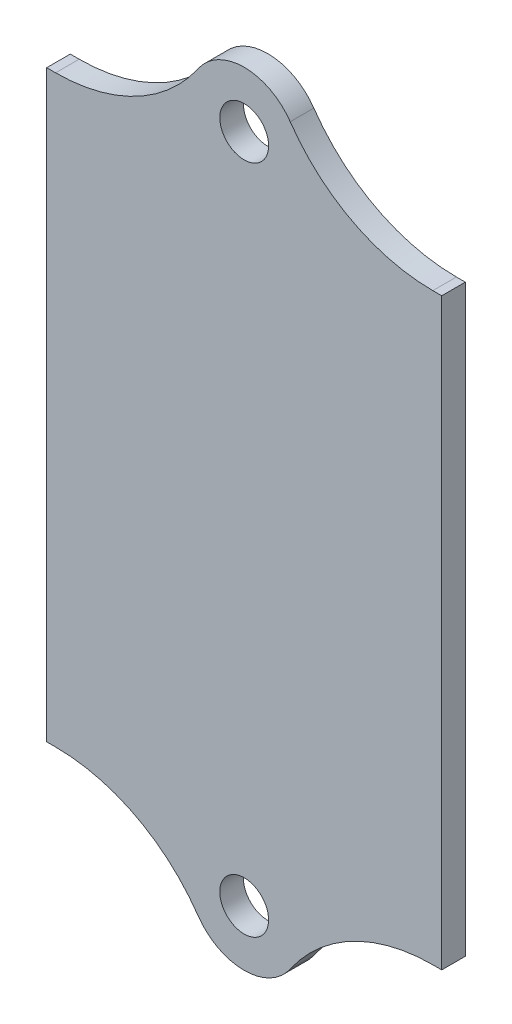
SolidWorks part; units mm, degrees
ref_plane "Front" through (0, 0, 0) normal (0, 0, 1) x (1, 0, 0)
ref_plane "Top" through (0, 0, 0) normal (0, 1, 0) x (1, 0, 0)
ref_plane "Side" through (0, 0, 0) normal (1, 0, 0) x (0, 0, -1)
ref_axis "X_Axis" through (-20.1896, 0, 0) along (1, 0, 0)
ref_axis "Y_Axis" through (0, -14.8261, 0) along (0, 1, 0)
ref_axis "Z_Axis" through (0, 0, -19.842) along (0, 0, 1)
sketch "Sketch1" plane through (0, 0, 0) normal (0, 0, 1) x (1, 0, 0)
  line L1 (-10.3513, 8) -> (-10.3513, 45.1)
  line L17 (-9.5513, 21.796) -> (-9.5513, 44.3)
  line L18 (-9.5513, 44.3) -> (13.9487, 44.3)
  line L19 (13.9487, 44.3) -> (13.9487, 8.8)
  line L20 (13.9487, 8.8) -> (-9.5513, 8.8)
  line L21 (-9.5513, 8.8) -> (-9.5513, 11.8167)
  line L22 (-9.5513, 11.8167) -> (-10.3513, 11.8167)
  line L23 (-10.3513, 11.8167) -> (-10.3513, 8)
  line L24 (-10.3513, 8) -> (-9.7863, 8)
  line L25 (14.1837, 8) -> (14.7487, 8)
  line L26 (14.7487, 8) -> (14.7487, 45.1)
  line L27 (14.7487, 45.1) -> (14.323, 45.1)
  line L30 (-9.9257, 45.1) -> (-10.3513, 45.1)
  line L31 (-10.3513, 45.1) -> (-10.3513, 21.796)
  line L40 (-10.3513, 8) -> (-9.7863, 8)
  line L41 (14.1837, 8) -> (14.7487, 8)
  line L42 (14.7487, 8) -> (14.7487, 45.1)
  line L43 (14.7487, 45.1) -> (14.323, 45.1)
  line L46 (-9.9257, 45.1) -> (-10.3513, 45.1)
  line L162 (-10.3513, 21.796) -> (-9.5513, 21.796)
  line L1118 (14.323, 45.1) -> (14.1837, 45.1)
  line L1119 (14.323, 45.1) -> (14.1837, 45.1)
  line L1120 (-9.7863, 45.1) -> (-9.9257, 45.1)
  line L1121 (-9.7863, 45.1) -> (-9.9257, 45.1)
  arc A6 (-0.7255, 3.2371) -> (-9.7863, 8) centre (-9.7863, -3) ccw
  arc A7 (-0.7255, 3.2371) -> (5.1229, 3.2371) centre (2.1987, 5.25) ccw
  arc A8 (14.1837, 8) -> (5.1229, 3.2371) centre (14.1837, -3) ccw
  arc A9 (5.1229, 49.8629) -> (14.1837, 45.1) centre (14.1837, 56.1) ccw
  arc A11 (5.1229, 49.8629) -> (14.1837, 45.1) centre (14.1837, 56.1) ccw
  arc A12 (-0.7255, 3.2371) -> (-9.7863, 8) centre (-9.7863, -3) ccw
  arc A13 (-0.7255, 3.2371) -> (5.1229, 3.2371) centre (2.1987, 5.25) ccw
  arc A14 (14.1837, 8) -> (5.1229, 3.2371) centre (14.1837, -3) ccw
  arc A415 (5.1229, 49.8629) -> (-0.7255, 49.8629) centre (2.1987, 47.85) ccw
  arc A423 (5.1229, 49.8629) -> (-0.7255, 49.8629) centre (2.1987, 47.85) ccw
  arc A424 (-9.7863, 45.1) -> (-0.7255, 49.8629) centre (-9.7863, 56.1) ccw
  arc A425 (-9.7863, 45.1) -> (-0.7255, 49.8629) centre (-9.7863, 56.1) ccw
  dimension "D1" = 0
extrude "Boss-Extrude1" add sketch "Sketch1" along normal blind 1.5
sketch "Sketch2" plane through (0, 0, 1.5) normal (0, 0, 1) x (1, 0, 0)
  circle A0 centre (2.1987, 47.85) radius 1.55
  circle A1 centre (2.1987, 5.25) radius 1.55
  dimension "D1" = 3.1
extrude "Cut-Extrude1" cut sketch "Sketch2" against normal through all
